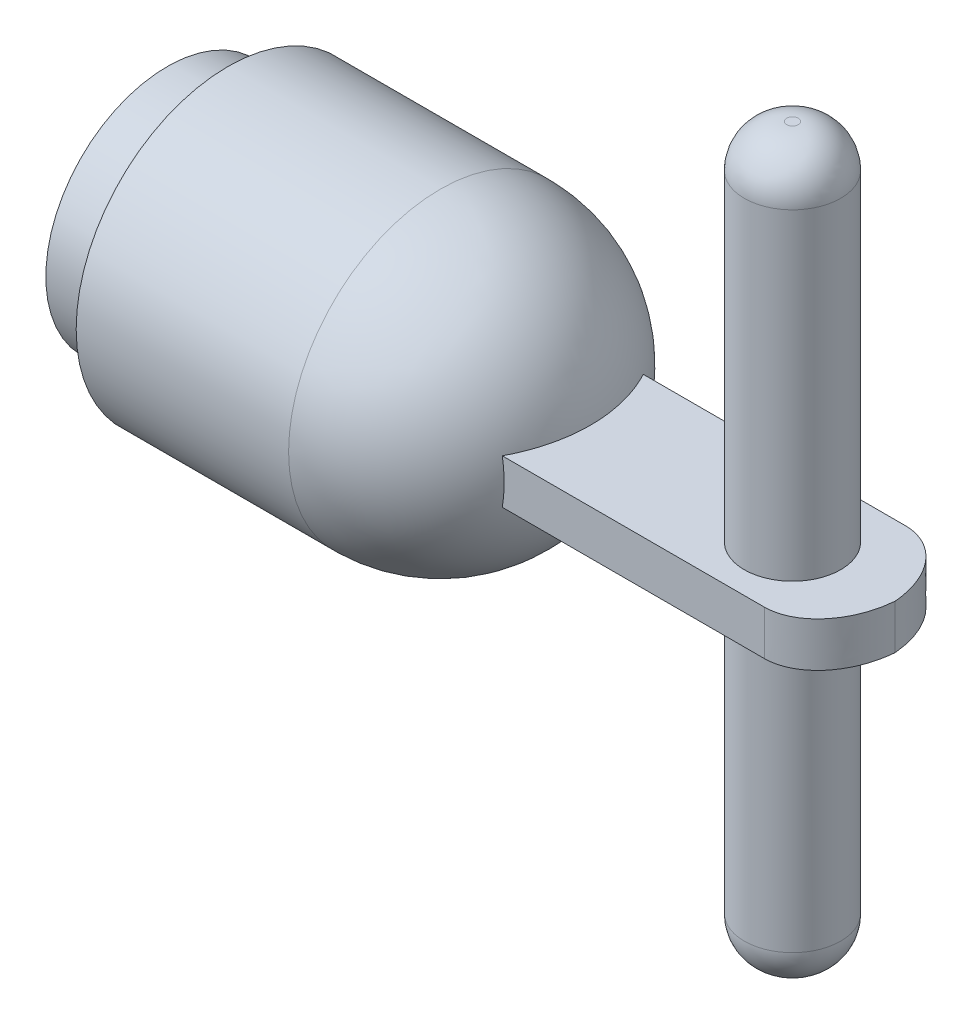
SolidWorks part; units mm, degrees
ref_plane "Front Plane" through (0, 0, 0) normal (0, 0, 1) x (1, 0, 0)
ref_plane "Top Plane" through (0, 0, 0) normal (0, 1, 0) x (1, 0, 0)
ref_plane "Right Plane" through (0, 0, 0) normal (1, 0, 0) x (0, 0, -1)
sketch "Sketch1" plane through (0, 0, 0) normal (1, 0, 0) x (0, 0, -1)
  circle A0 centre (0, 0) radius 20
extrude "Boss-Extrude1" add sketch "Sketch1" along normal blind 10
sketch "Sketch2" plane through (10, 0, 0) normal (1, 0, 0) x (0, 0, -1)
  circle A0 centre (0, 0) radius 25
extrude "Boss-Extrude2" add sketch "Sketch2" along normal blind 60
fillet "Fillet1" radius 25 1 edges at (70, 0, -25)
sketch "Sketch3" plane through (0, 0, 0) normal (-1, 0, 0) x (0, 0, 1)
  line L1 (-11.6204, 3.6716) -> (11.6204, 3.6716)
  line L2 (-11.6204, 3.6716) -> (-11.6204, -3.6716)
  line L3 (-11.6204, -3.6716) -> (11.6204, -3.6716)
  line L4 (11.6204, 3.6716) -> (11.6204, -3.6716)
  line L5 (-11.6204, 3.6716) -> (11.6204, -3.6716) construction
  line L6 (-11.6204, -3.6716) -> (11.6204, 3.6716) construction
  point P0 (0, 0)
extrude "Boss-Extrude3" add sketch "Sketch3" against normal blind 120
sketch "Sketch4" plane through (0, 3.6716, 0) normal (0, 1, 0) x (1, 0, 0)
  circle A0 centre (103.0308, 0) radius 7.9434
extrude "Boss-Extrude4" add sketch "Sketch4" along normal mid plane 120
fillet "Fillet2" radius 7 1 edges at (103.0308, 63.6716, 7.9434)
fillet "Fillet3" radius 7 1 edges at (103.0308, -56.3284, 7.9434)
fillet "Fillet4" radius 13 2 edges at (120, 0, -11.6204) (120, 0, 11.6204) second distance 10 first distance on face at (120, 0, 0)
